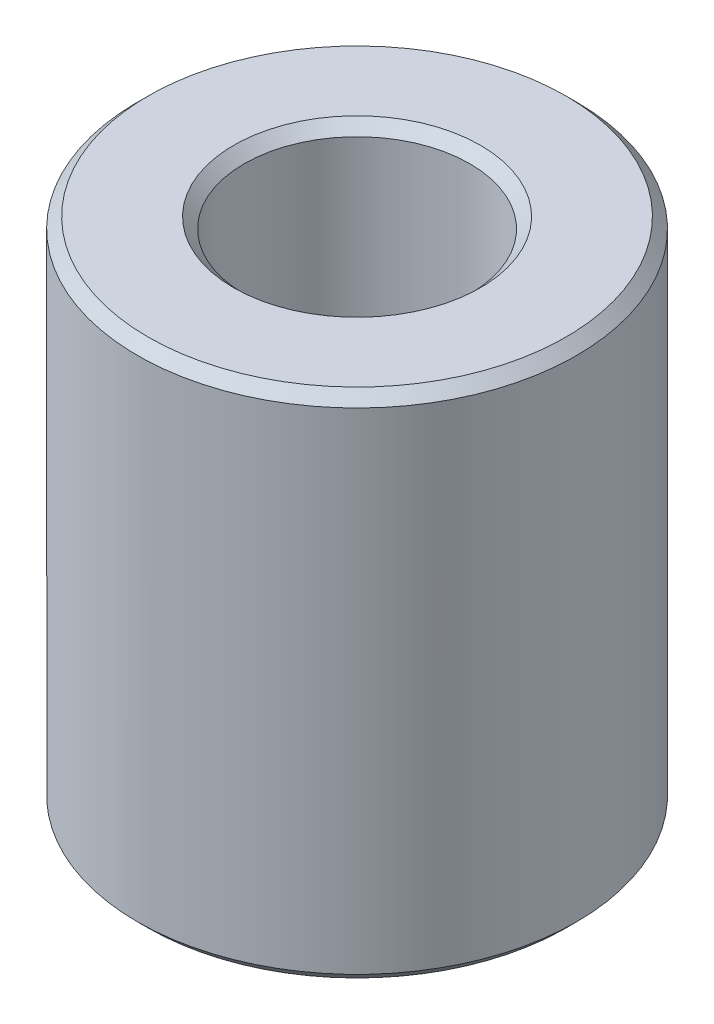
SolidWorks part; units mm, degrees
ref_plane "Front Plane" through (0, 0, 0) normal (0, 0, 1) x (1, 0, 0)
ref_plane "Top Plane" through (0, 0, 0) normal (0, 1, 0) x (1, 0, 0)
ref_plane "Right Plane" through (0, 0, 0) normal (1, 0, 0) x (0, 0, -1)
sketch "Sketch1" plane through (0, 0, 0) normal (0, 1, 0) x (1, 0, 0)
  circle A0 centre (0, 0) radius 47.5
  dimension "SLEEVE_OD" = 95
extrude "Boss-Extrude1" add sketch "Sketch1" along normal blind 110.7381
sketch "Sketch2" plane through (0, 0, 0) normal (0, 1, 0) x (1, 0, 0)
  circle A0 centre (0, 0) radius 24.4049
  dimension "BORE_D" = 48.8098
extrude "Cut-Extrude1" cut sketch "Sketch2" along normal through all
chamfer "Chamfer1" distance 2.3008 angle 45 4 edges at (0, 110.7381, 24.4049) (0, 0, 24.4049) (0, 0, 47.5) (0, 110.7381, 47.5)
